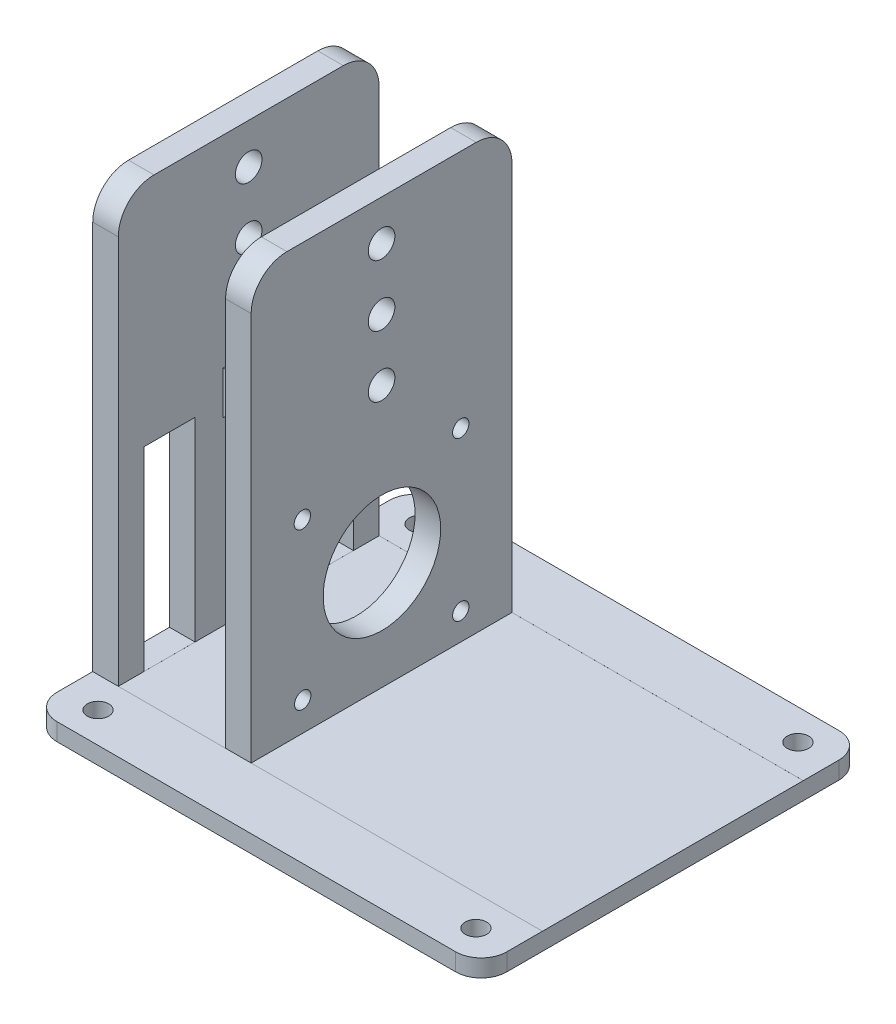
SolidWorks part; units mm, degrees
ref_plane "Front Plane" through (0, 0, 0) normal (0, 0, 1) x (1, 0, 0)
ref_plane "Top Plane" through (0, 0, 0) normal (0, 1, 0) x (1, 0, 0)
ref_plane "Right Plane" through (0, 0, 0) normal (1, 0, 0) x (0, 0, -1)
sketch "Sketch1" plane through (0, 0, 0) normal (0, 1, 0) x (1, 0, 0)
  line L1 (-44.0031, -25.5222) -> (44.0031, -25.5222)
  line L2 (-44.0031, -25.5222) -> (-44.0031, 25.5222)
  line L3 (-44.0031, 25.5222) -> (44.0031, 25.5222)
  line L4 (44.0031, -25.5222) -> (44.0031, 25.5222)
  line L5 (-44.0031, -25.5222) -> (44.0031, 25.5222) construction
  line L6 (-44.0031, 25.5222) -> (44.0031, -25.5222) construction
  point P0 (0, 0)
extrude "Boss-Extrude1" add sketch "Sketch1" along normal blind 3.4061
sketch "Sketch2" plane through (0, 3.4061, 0) normal (0, 1, 0) x (1, 0, 0)
  line L0 (-13.0031, 25.5222) -> (-18.0031, 25.5222)
  line L1 (44.0031, 25.5222) -> (-44.0031, 25.5222) construction
  line L2 (-18.0031, 25.5222) -> (-18.0031, -25.5222)
  line L3 (-44.0031, -25.5222) -> (44.0031, -25.5222) construction
  line L4 (-18.0031, -25.5222) -> (-13.0031, -25.5222)
  line L5 (-13.0031, -25.5222) -> (-13.0031, 25.5222)
  line L6 (-44.0031, 25.5222) -> (-44.0031, -25.5222) construction
  dimension "D1" = 5
  dimension "D2" = 26
extrude "Boss-Extrude3" add sketch "Sketch2" along normal blind 83.1809
sketch "Sketch8" plane through (-13.0031, 0, 0) normal (1, 0, 0) x (0, 0, -1)
  circle A0 centre (0.0714, 24.5561) radius 11.5
extrude "Cut-Extrude3" cut sketch "Sketch8" against normal through all
sketch "Sketch9" plane through (-13.0031, 0, 0) normal (1, 0, 0) x (0, 0, -1)
  circle A0 centre (-15.4286, 9.0561) radius 1.6
  circle A1 centre (-15.5, 39.65) radius 1.6
  circle A2 centre (15.5, 39.65) radius 1.6
  circle A3 centre (15.5, 8.65) radius 1.6
extrude "Cut-Extrude4" cut sketch "Sketch9" against normal through all both and the other way through all
sketch "Sketch17" plane through (-44.0031, -0.0607, 0) normal (-1, 0, 0) x (0, 0, 1)
  line L9 (-25.5222, 0.0607) -> (25.5222, 0.0607)
  line L10 (-25.5222, 0.0607) -> (-25.5222, 86.6476)
  line L11 (-25.5222, 86.6476) -> (25.5222, 86.6476)
  line L12 (25.5222, 0.0607) -> (25.5222, 86.6476)
extrude "Boss-Extrude4" add sketch "Sketch17" against normal blind 5
sketch "Sketch20" plane through (-13.0031, 0, 0) normal (1, 0, 0) x (0, 0, -1)
  circle A0 centre (0, 78.6812) radius 2.605
  circle A1 centre (0, 66.6812) radius 2.605
  circle A2 centre (0, 54.6812) radius 2.605
  dimension "5.2" = 5.21
  dimension "D2" = 5.21
ref_plane "Plane1" through (-39.0031, 86.587, 25.5222) normal (-1, 0, 0) x (0, 0, 1)
fillet "Fillet2" radius 7 1 edges at (-15.5031, 86.587, 25.5222)
fillet "Fillet4" radius 7 1 edges at (-41.5031, 86.587, 25.5222)
fillet "Fillet5" radius 7 1 edges at (-15.5031, 86.587, -25.5222)
fillet "Fillet6" radius 7 1 edges at (-41.5031, 86.587, -25.5222)
sketch "Sketch27" plane through (0, 0, 0) normal (0, -1, 0) x (1, 0, 0)
  line L0 (44.0031, 25.5222) -> (44.0031, -25.5222) construction
  line L1 (-44.0031, -37.5) -> (44.0031, -37.5)
  line L2 (-44.0031, -37.5) -> (-44.0031, -25.5222)
  line L3 (-44.0031, 37.5) -> (44.0031, 37.5)
  line L4 (44.0031, -37.5) -> (44.0031, -25.5222)
  line L5 (-44.0031, -37.5) -> (0, 0) construction
  line L6 (-44.0031, 37.5) -> (-29.9481, 25.5222) construction
  line L7 (-44.0031, 25.5222) -> (44.0031, 25.5222)
  line L9 (44.0031, -25.5222) -> (-44.0031, -25.5222)
  line L11 (-44.0031, 25.5222) -> (-44.0031, 37.5)
  line L12 (0, 0) -> (44.0031, -37.5) construction
  line L13 (29.9481, 25.5222) -> (44.0031, 37.5) construction
  line L14 (44.0031, 25.5222) -> (44.0031, 37.5)
  point P0 (0, 0)
sketch "Sketch28" plane through (0, 3.4061, 0) normal (0, 1, 0) x (1, 0, 0)
  circle A0 centre (36.9756, 31.5111) radius 2.1
  circle A1 centre (-36.9756, 31.5111) radius 2.1
  circle A2 centre (-36.9756, -31.5111) radius 2.1
  circle A3 centre (36.9756, -31.5111) radius 2.1
extrude "Boss-Extrude7" add sketch "Sketch27" against normal blind 3.41
extrude "Cut-Extrude10" cut sketch "Sketch28" against normal through all both and the other way through all
sketch "Sketch29" plane through (-39.0031, 0, 0) normal (1, 0, 0) x (0, 0, -1)
  line L0 (0, 0) -> (0, 86.587)
  line L1 (0.9742, 44.1597) -> (-4.0258, 44.1597)
  line L3 (-4.0258, 47.1046) -> (5, 47.1046)
  line L5 (5, 44.1597) -> (0.9742, 44.1597)
  line L6 (-18.5222, 86.587) -> (18.5222, 86.587) construction
  line L7 (0, 44.1597) -> (-5, 44.1597)
  line L8 (-5, 44.1597) -> (-5, 47.1046)
  line L9 (-5, 47.1046) -> (5, 47.1046)
  line L10 (5, 47.1046) -> (5, 44.1597)
  line L11 (5, 44.1597) -> (0, 44.1597)
fillet "Fillet7" radius 5 4 edges at (44.0031, 1.705, -37.5) (-44.0031, 1.705, -37.5) (-44.0031, 1.705, 37.5) (44.0031, 1.705, 37.5)
extrude "Cut-Extrude12" cut sketch "Sketch20" against normal through all both and the other way through all
extrude "Boss-Extrude10" add sketch "Sketch29" along normal blind 25 contours L10 L3 L0 L1 L5 | L9 L8 L7 L1 L0 L3 region at (-39.0031, 45.6321, 2.5) region at (-39.0031, 45.6321, -2.5)
sketch "Sketch34" plane through (0, 0, 5) normal (0, 0, 1) x (1, 0, 0)
  line L1 (-18.0031, 44.1597) -> (-39.0031, 44.1597) construction
  line L2 (-33.5031, 44.1597) -> (-39.0031, 38.6597)
  line L3 (-39.0031, 141.587) -> (-39.0031, 31.587) construction
  line L4 (-39.0031, 38.6597) -> (-39.0031, 41.6597)
  line L5 (-39.0031, 41.6597) -> (-36.5031, 44.1597)
  line L6 (-36.5031, 44.1597) -> (-33.5031, 44.1597)
  line L8 (-23.6642, 44.1597) -> (-18.0031, 38.4985)
  line L9 (-18.0031, 79.587) -> (-18.0031, 3.41) construction
  line L10 (-18.0031, 38.4985) -> (-18.0031, 41.4985)
  line L11 (-18.0031, 41.4985) -> (-20.6642, 44.1597)
  line L12 (-20.6642, 44.1597) -> (-23.6642, 44.1597)
extrude "Boss-Extrude11" add sketch "Sketch34" against normal blind 10
sketch "Sketch35" plane through (-44.0031, 0, 0) normal (-1, 0, 0) x (0, 0, 1)
  line L3 (-20.5, 41.4985) -> (-10.5, 41.4985)
  line L6 (10.5, 3.41) -> (20.5, 3.41)
  line L9 (-20.5, 3.41) -> (-10.5, 3.41)
  line L11 (10.5, 41.4985) -> (20.5, 41.4985)
  line L12 (20.5, 41.4985) -> (20.5, 3.41)
  line L13 (15.5, 41.4985) -> (20.5, 41.4985)
  line L14 (20.5, 41.4985) -> (10.5, 41.4985)
  line L15 (10.5, 41.4985) -> (10.5, 3.41)
  line L16 (10.5, 3.41) -> (20.5, 3.41)
  line L17 (20.5, 3.41) -> (20.5, 41.4985)
  line L18 (-20.5, 3.41) -> (-20.5, 41.4985)
  line L19 (-10.5, 3.41) -> (-20.5, 3.41)
  line L20 (-10.5, 41.4985) -> (-10.5, 3.41)
  line L21 (-20.5, 41.4985) -> (-10.5, 41.4985)
  line L22 (10.5, 41.4985) -> (20.5, 41.4985)
extrude "Cut-Extrude14" cut sketch "Sketch35" against normal blind 11 contours L11 L15 L6 L12 | L20 L3 L18 L9 region at (-44.0031, 22.4542, -15.5) region at (-44.0031, 22.4542, 15.5)
sketch "Sketch36" plane through (0, 0, 5) normal (0, 0, 1) x (1, 0, 0)
  line L0 (-36.5031, 44.1597) -> (-39.0031, 44.1597)
  line L1 (-39.0031, 141.587) -> (-39.0031, 31.587) construction
  line L2 (-39.0031, 44.1597) -> (-39.0031, 41.6597)
  line L3 (-36.5031, 44.1597) -> (-39.0031, 41.6597) construction
  line L4 (-39.0031, 41.6597) -> (-36.5031, 44.1597)
  line L5 (-20.6642, 44.1597) -> (-18.0031, 44.1597)
  line L6 (-18.0031, 44.1597) -> (-18.0031, 41.4985)
  line L7 (-18.0031, 79.587) -> (-18.0031, 3.41) construction
  line L8 (-18.0031, 41.4985) -> (-20.6642, 44.1597)
extrude "Boss-Extrude12" add sketch "Sketch36" against normal blind 10
